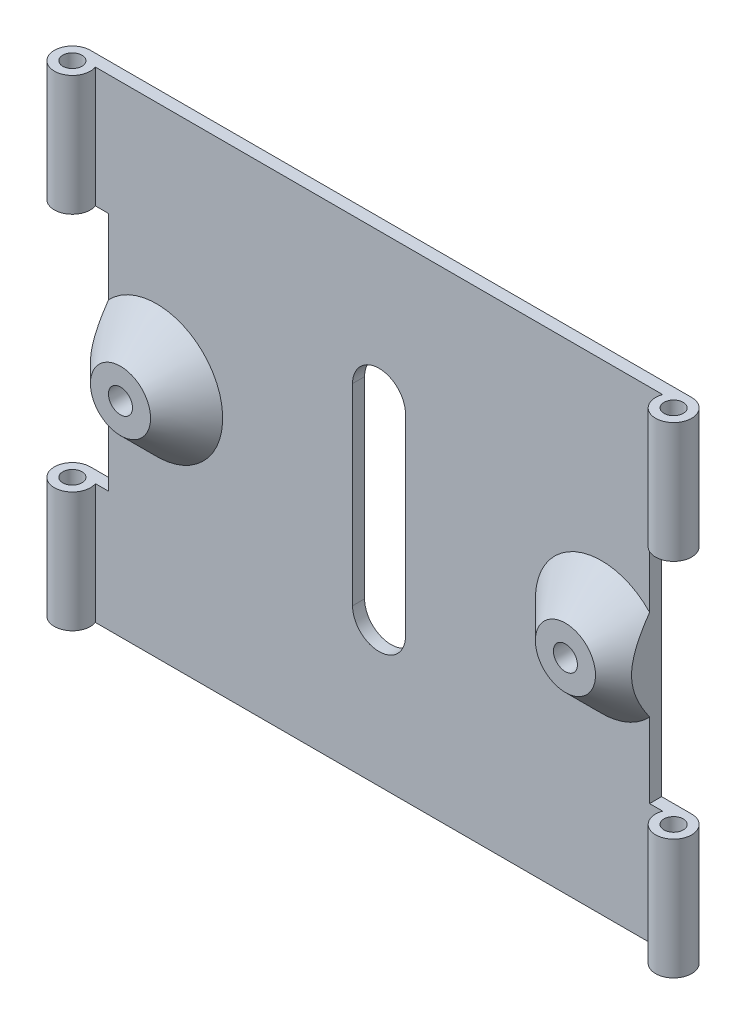
SolidWorks part; units mm, degrees
ref_plane "Front Plane" through (0, 0, 0) normal (0, 0, 1) x (1, 0, 0)
ref_plane "Top Plane" through (0, 0, 0) normal (0, 1, 0) x (1, 0, 0)
ref_plane "Right Plane" through (0, 0, 0) normal (1, 0, 0) x (0, 0, -1)
sketch "Sketch1" plane through (0, 0, 0) normal (0, 0, 1) x (1, 0, 0)
  line L0 (0, -0.1015) -> (0, 25.3985) construction
  line L1 (-25, -20) -> (25, -20)
  line L2 (-25, -20) -> (-25, 20)
  line L3 (-25, 20) -> (25, 20)
  line L4 (25, -20) -> (25, 20)
  line L5 (-25, -20) -> (25, 20) construction
  line L6 (-25, 20) -> (25, -20) construction
  line L7 (0, 7.8985) -> (0, -8.1015) construction
  line L8 (2.2, 7.8985) -> (2.2, -8.1015)
  line L9 (-2.2, 7.8985) -> (-2.2, -8.1015)
  arc A0 (2.2, 7.8985) -> (-2.2, 7.8985) centre (0, 7.8985) ccw
  arc A1 (-2.2, -8.1015) -> (2.2, -8.1015) centre (0, -8.1015) ccw
  point P0 (0, 0)
  point P10 (0, -0.1015)
  dimension "D3" = 2.2
  dimension "D4" = 16
  dimension "D1" = 50
  dimension "D2" = 40
  dimension "D5" = 25.5
extrude "Boss-Extrude1" add sketch "Sketch1" along normal blind 1
sketch "Sketch2" plane through (0, 20, 0) normal (0, 1, 0) x (1, 0, 0)
  circle A0 centre (-25, -1.5) radius 1.5
  circle A1 centre (25, -1.5) radius 1.5
  dimension "D1" = 3
  dimension "D2" = 3
extrude "Boss-Extrude2" add sketch "Sketch2" against normal up to surface (40 mm away) up to face at (0, -20, 0.5)
sketch "Sketch3" plane through (0, 20, 0) normal (0, 1, 0) x (1, 0, 0)
  circle A0 centre (-25, -1.5) radius 0.8
  circle A1 centre (25, -1.5) radius 0.8
  dimension "D1" = 1.6
  dimension "D2" = 1.6
extrude "Cut-Extrude1" cut sketch "Sketch3" against normal through all
sketch "Sketch4" plane through (0, 0, 1) normal (0, 0, 1) x (1, 0, 0)
  line L0 (-22.5, 10) -> (-22.5, 20) construction
  line L1 (-22.5, 10) -> (-52.4859, 10)
  line L2 (-22.5, 10) -> (-22.5, -10)
  line L3 (-22.5, -10) -> (-52.4859, -10)
  line L4 (-52.4859, 10) -> (-52.4859, -10)
  line L5 (22.5, 10) -> (33.1663, 10)
  line L6 (22.5, 10) -> (22.5, -10)
  line L7 (22.5, -10) -> (33.1663, -10)
  line L8 (33.1663, 10) -> (33.1663, -10)
  line L9 (23.5858, 20) -> (-23.5858, 20) construction
  line L10 (-22.5, -10) -> (-22.5, -20) construction
  line L11 (-23.5858, -20) -> (23.5858, -20) construction
  line L12 (-24, 20) -> (-24, -20) construction
  line L13 (24, -20) -> (24, 20) construction
  dimension "D1" = 20
  dimension "D2" = 1.5
  dimension "D3" = 1.5
extrude "Cut-Extrude2" cut sketch "Sketch4" against normal through all both and the other way through all
sketch "Sketch5" plane through (0, 0, 1) normal (0, 0, 1) x (1, 0, 0)
  line L0 (-22.5, 0) -> (22.5, 0) construction
  line L1 (-22.5, 10) -> (-22.5, -10) construction
  line L2 (22.5, -10) -> (22.5, 10) construction
  circle A0 centre (-18.5, 0) radius 1
  circle A1 centre (18.5, 0) radius 1
  circle A2 centre (-18.5, 0) radius 2.5
  circle A3 centre (18.5, 0) radius 2.5
  dimension "D1" = 37
  dimension "D3" = 2
  dimension "D4" = 5
  dimension "D5" = 5
  dimension "D2" = 18.5
extrude "Boss-Extrude3" add sketch "Sketch5" along normal blind 3
chamfer "Chamfer1" distance 3 angle 45 2 edges at (16, 0, 1) (-21, 0, 1)
